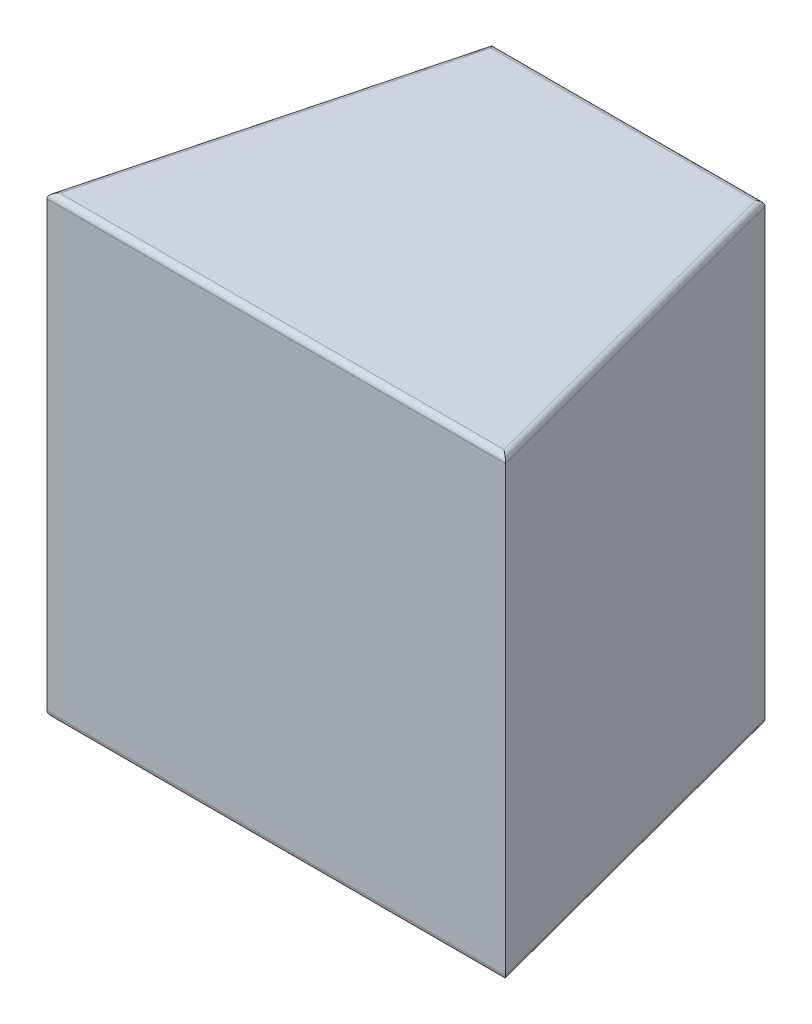
SolidWorks part; units mm, degrees
ref_plane "Front Plane" through (0, 0, 0) normal (0, 0, 1) x (1, 0, 0)
ref_plane "Top Plane" through (0, 0, 0) normal (0, 1, 0) x (1, 0, 0)
ref_plane "Right Plane" through (0, 0, 0) normal (1, 0, 0) x (0, 0, -1)
sketch "Sketch1" plane through (0, 0, 0) normal (0, 1, 0) x (1, 0, 0)
  line L0 (0, 0) -> (0, 17.6521) construction
  line L1 (0, 0) -> (17.6247, 0) construction
  line L2 (-20.175, -15.5) -> (-12, 15.5)
  line L3 (-12, 15.5) -> (12, 15.5)
  line L4 (12, 15.5) -> (20.175, -15.5)
  line L5 (20.175, -15.5) -> (-20.175, -15.5)
  dimension "D1" = 24
  dimension "D2" = 31
  dimension "D3" = 40.35
extrude "Boss-Extrude1" add sketch "Sketch1" along normal blind 40
fillet "Fillet1" radius 0.5 8 edges at (16.0875, 0, 0) (0, 0, -15.5) (-16.0875, 0, 0) (0, 0, 15.5) (-16.0875, 40, 0) (0, 40, -15.5) (16.0875, 40, 0) (0, 40, 15.5)
